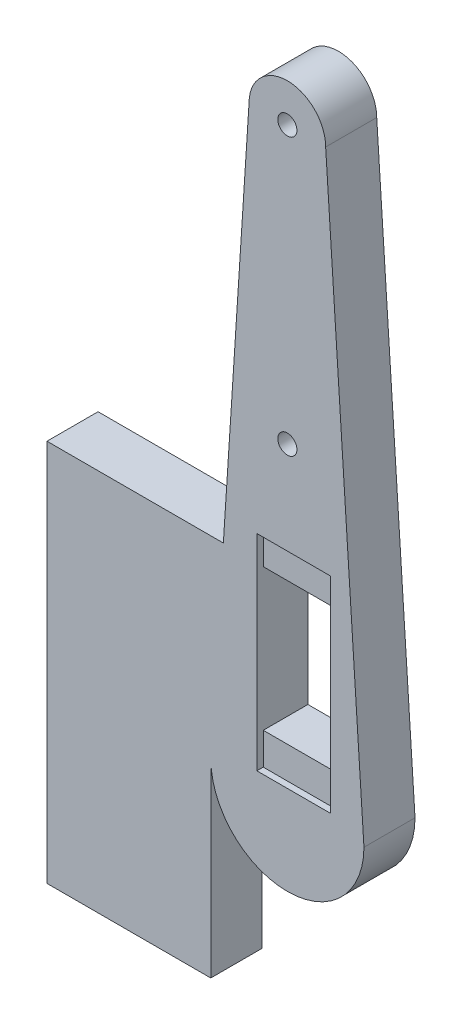
SolidWorks part; units mm, degrees
ref_plane "Front Plane" through (0, 0, 0) normal (0, 0, 1) x (1, 0, 0)
ref_plane "Top Plane" through (0, 0, 0) normal (0, 1, 0) x (1, 0, 0)
ref_plane "Right Plane" through (0, 0, 0) normal (1, 0, 0) x (0, 0, -1)
sketch "Sketch1" plane through (0, 0, 0) normal (0, 0, 1) x (1, 0, 0)
  line L0 (12.829, 57.8707) -> (12.829, -34.1293) construction
  line L1 (18.829, 57.8707) -> (24.829, -34.1293)
  line L2 (6.829, 57.8707) -> (2.8024, -3.8707)
  line L3 (2.8024, -3.8707) -> (-24.829, -3.8707)
  line L4 (0.829, -34.1293) -> (0.829, -63.8707)
  line L5 (0.829, -63.8707) -> (-24.829, -63.8707)
  line L6 (-24.829, -3.8707) -> (-24.829, -63.8707)
  arc A0 (0.829, -34.1293) -> (24.829, -34.1293) centre (12.829, -34.1293) ccw
  arc A1 (18.829, 57.8707) -> (6.829, 57.8707) centre (12.829, 57.8707) ccw
  circle A2 centre (12.829, 57.8707) radius 1.5
  circle A3 centre (12.829, 14.5707) radius 1.5
  point P2 (12.829, -7.4052)
extrude "Boss-Extrude1" add sketch "Sketch1" along normal blind 8
sketch "Sketch2" plane through (0, 0, 8) normal (0, 0, 1) x (1, 0, 0)
  line L0 (13.8024, -4.9493) -> (8.0524, -4.9493)
  line L1 (19.5524, -4.9493) -> (19.5524, -10.6993)
  line L2 (19.5524, -10.6993) -> (19.5524, -27.1493)
  line L3 (8.0524, -4.9493) -> (19.5524, -4.9493)
  line L4 (19.5524, -4.9493) -> (13.8024, -4.9493)
  line L5 (19.5524, 0.0507) -> (19.5524, -4.9493)
  line L6 (8.0524, 0.0507) -> (19.5524, 0.0507)
  line L7 (8.0524, 0.0507) -> (8.0524, -4.9493)
  line L8 (8.0524, -4.9493) -> (8.0524, -10.6993)
  line L9 (8.0524, -10.6993) -> (8.0524, -27.1493)
  line L10 (19.5524, -27.1493) -> (8.0524, -27.1493)
  line L11 (19.5524, -32.1493) -> (19.5524, -27.1493)
  line L12 (8.0524, -32.1493) -> (8.0524, -27.1493)
  line L13 (8.0524, -32.1493) -> (19.5524, -32.1493)
  line L14 (8.3222, 4.2707) -> (15.2348, 4.2707)
  arc A0 (11.8508, -16.108) -> (15.754, -16.108) centre (13.8024, -16.6993) ccw
  circle A1 centre (13.8024, -10.6993) radius 2.25
  arc A2 (11.8508, -16.108) -> (15.754, -16.108) centre (13.8024, -16.6993) ccw
  arc A3 (15.754, -16.108) -> (11.8508, -16.108) centre (13.8024, -10.6993) ccw
  arc A4 (13.8024, -4.9493) -> (8.0524, -10.6993) centre (13.8024, -10.6993) ccw
  circle A5 centre (13.8024, -1.9493) radius 1.25
  circle A6 centre (13.8024, -30.1493) radius 1.25
  point P33 (13.8024, -10.6993)
extrude "Cut-Extrude1" cut sketch "Sketch2" against normal blind 20 and the other way through all contours A3 L9 L10 L2 A0 | A3 A0 A1 | A1 | A3 L1 L3 | A3 L0 L8 region at (9.3368, -6.2337, 8) region at (18.268, -6.2337, 8) region at (17.7413, -6.7604, 8) region at (13.8024, -21.3456, 8) region at (13.8024, -10.6993, 8)
extrude "Cut-Extrude2" cut sketch "Sketch2<3>" against normal blind 1 contours L6 L7 L0 L3 L5 A5 | L12 L13 L11 L10 A6 | A6 | A5 region at (10.9274, -4.8239, 8) region at (19.427, -29.6493, 8) region at (13.8024, -30.1493, 8)
sketch "Sketch2<3>" plane through (0, 0, 8) normal (0, 0, 1) x (1, 0, 0) same geometry as "Sketch2"
